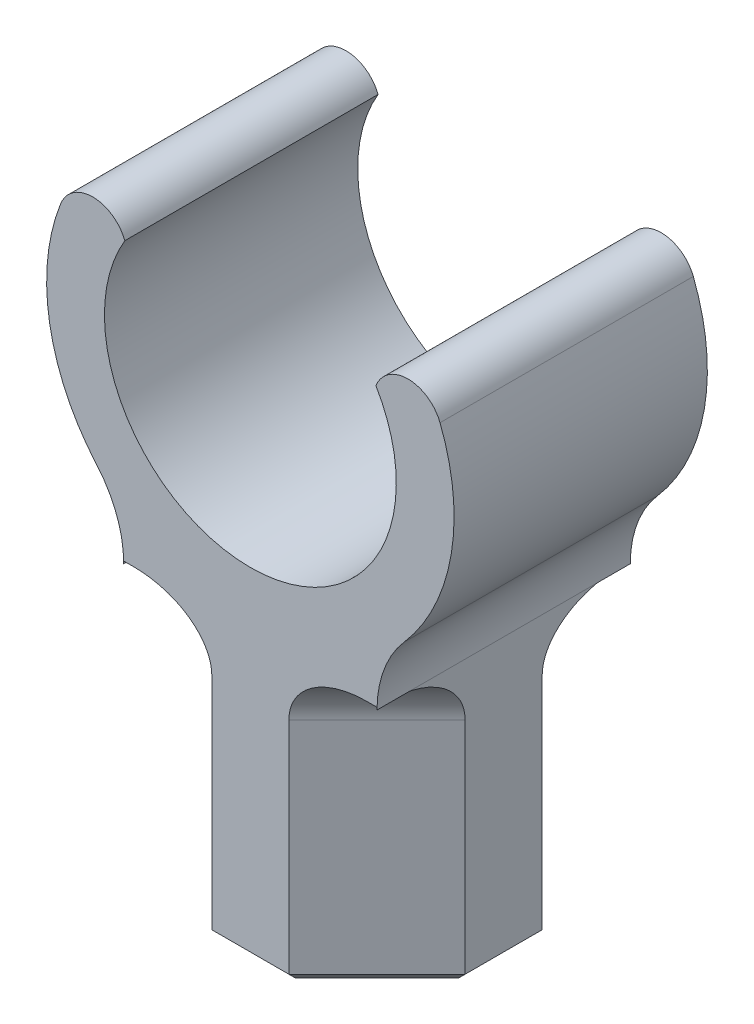
SolidWorks part; units mm, degrees
ref_plane "Front Plane" through (0, 0, 0) normal (0, 0, 1) x (1, 0, 0)
ref_plane "Top Plane" through (0, 0, 0) normal (0, 1, 0) x (1, 0, 0)
ref_plane "Right Plane" through (0, 0, 0) normal (1, 0, 0) x (0, 0, -1)
sketch "Sketch1" plane through (0, 0, 0) normal (0, 0, 1) x (1, 0, 0)
  line L6 (-28.7739, -13.25) -> (44.2672, -13.25) construction
  line L10 (-11.5, -14.4914) -> (-11.5, -44.4914)
  line L11 (-24.5505, 6.75) -> (34.718, 6.75) construction
  line L13 (-11.5, -44.4914) -> (11.5, -44.4914)
  line L14 (11.5, -14.4914) -> (11.5, -44.4914)
  arc A0 (-11.4018, 6.75) -> (11.4018, 6.75) centre (0, 0) ccw
  arc A1 (11.5, -14.4914) -> (17.2246, 6.75) centre (0, 0) ccw
  arc A6 (-17.2246, 6.75) -> (-11.5, -14.4914) centre (0, 0) ccw
  arc A7 (-17.2246, 6.75) -> (-11.4018, 6.75) centre (-14.3132, 5.6091) cw
  arc A8 (17.2246, 6.75) -> (11.4018, 6.75) centre (14.3132, 5.6091) ccw
  dimension "D1" = 26.5
  dimension "D2" = 37
  dimension "D3" = 23
  dimension "D4" = 30
  dimension "D5" = 20
extrude "Boss-Extrude1" add sketch "Sketch1" along normal blind 23
fillet "Fillet1" radius 10 2 edges at (-11.5, -14.4914, 11.5) (11.5, -14.4914, 11.5)
sketch "Sketch2" plane through (0, -44.4914, 0) normal (0, -1, 0) x (1, 0, 0)
  line L1 (-6.5, 5) -> (6.5, 5)
  line L2 (-6.5, 5) -> (-6.5, 18)
  line L3 (-6.5, 18) -> (6.5, 18)
  line L4 (6.5, 5) -> (6.5, 18)
  line L5 (11.5, 23) -> (11.5, 0) construction
  line L6 (-11.5, 23) -> (-11.5, 0) construction
  line L8 (-11.5, 23) -> (11.5, 23) construction
  line L9 (-11.5, 0) -> (11.5, 0) construction
  dimension "D1" = 5
  dimension "D2" = 5
  dimension "D3" = 5
  dimension "D4" = 5
extrude "Cut-Extrude1" cut sketch "Sketch2" against normal blind 20
chamfer "Chamfer2" distance 3.5 angle 45 4 edges at (-6.5, -34.4914, 5) (6.5, -34.4914, 5) (6.5, -34.4914, 18) (-6.5, -34.4914, 18)
sketch "Sketch3" plane through (0, -44.4914, 0) normal (0, -1, 0) x (1, 0, 0)
  line L0 (11.5, 0) -> (11.5, 23) construction
  line L1 (-11.5, 0) -> (11.5, 0) construction
  line L2 (-11.5, 23) -> (-11.5, 0) construction
  line L3 (-11.5, 23) -> (11.5, 23) construction
  line L4 (11.5, 8) -> (11.5, 15)
  line L5 (-3.5, 0) -> (3.5, 0)
  line L6 (-11.5, 15) -> (-11.5, 8)
  line L7 (-3.5, 23) -> (3.5, 23)
  line L8 (-3.5, 23) -> (-11.5, 15)
  line L9 (11.5, 15) -> (3.5, 23)
  line L10 (3.5, 0) -> (11.5, 8)
  line L11 (-11.5, 8) -> (-3.5, 0)
  line M17 (-11.5, 0) -> (11.5, 0)
  line M18 (11.5, 0) -> (11.5, 23)
  line M19 (11.5, 23) -> (-11.5, 23)
  line M20 (-11.5, 23) -> (-11.5, 0)
extrude "Cut-Extrude2" cut sketch "Sketch3" against normal blind 26 contours L8 M19 M20 | L9 M18 M19 | L10 M17 M18 | L11 M20 M17 region at (8.8333, -44.4914, 2.6667) region at (8.8333, -44.4914, 20.3333) region at (-8.8333, -44.4914, 2.6667) region at (-8.8333, -44.4914, 20.3333)
chamfer "Chamfer3" distance 1 angle 45 16 edges at (-11.5, -44.4914, 11.5) (-7.5, -44.4914, 19) (0, -44.4914, 23) (7.5, -44.4914, 19) (11.5, -44.4914, 11.5) (7.5, -44.4914, 4) (0, -44.4914, 0) (-7.5, -44.4914, 4) (4.75, -44.4914, 6.75) (6.5, -44.4914, 11.5) (4.75, -44.4914, 16.25) (0, -44.4914, 18) (-4.75, -44.4914, 16.25) (-6.5, -44.4914, 11.5) (-4.75, -44.4914, 6.75) (0, -44.4914, 5)
fillet "Fillet2" radius 5 4 edges at (7.5, -18.4914, 4) (-7.5, -18.4914, 4) (-7.5, -18.4914, 19) (7.5, -18.4914, 19)
